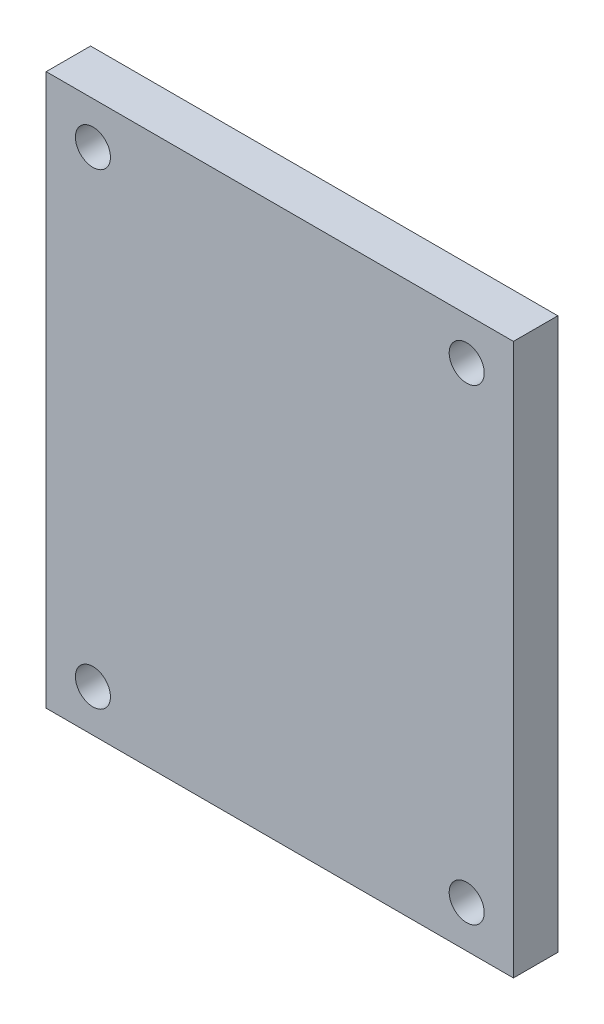
SolidWorks part; units mm, degrees
ref_plane "Front Plane" through (0, 0, 0) normal (0, 0, 1) x (1, 0, 0)
ref_plane "Top Plane" through (0, 0, 0) normal (0, 1, 0) x (1, 0, 0)
ref_plane "Right Plane" through (0, 0, 0) normal (1, 0, 0) x (0, 0, -1)
sketch "Sketch1" plane through (0, 0, 0) normal (0, 0, 1) x (1, 0, 0)
  line L0 (5.08, 55.372) -> (5.08, 4.572) construction
  line L1 (0, 0) -> (50.8, 0)
  line L2 (0, 0) -> (0, 59.944)
  line L3 (0, 59.944) -> (50.8, 59.944)
  line L4 (50.8, 0) -> (50.8, 59.944)
  line L5 (0, 29.972) -> (50.8, 29.972) construction
  line L6 (25.4, 59.944) -> (25.4, 29.972) construction
  circle A0 centre (5.08, 55.372) radius 1.905
  circle A1 centre (5.08, 4.572) radius 1.905
  circle A2 centre (45.72, 55.372) radius 1.905
  circle A3 centre (45.72, 4.572) radius 1.905
  dimension "D3" = 3.81
  dimension "D4" = 3.81
  dimension "D6" = 3.81
  dimension "D8" = 3.81
  dimension "D1" = 59.944
  dimension "D2" = 50.8
  dimension "D5" = 50.8
  dimension "D7" = 40.64
  dimension "D9" = 40.64
  dimension "D10" = 50.8
  dimension "D11" = 25.4
  dimension "D12" = 20.32
extrude "Boss-Extrude1" add sketch "Sketch1" along normal blind 4.826
equation "\"MDF\"= 0.19in"
equation "\"PVCID\" = 2.067in"
equation "\"PVCOD\" = 2.375in"
equation "\"GenDiameter\"= 60mm"
equation "\"GenCutDiameter\" = 1.8in"
equation "\"GenCutDistance\" = 1"
equation "\"TowerHeight\" = 6in"
equation "\"TowerFrontBase\" = 3in"
equation "\"FunnelHeight\" = 1in"
equation "\"FunnelAngle\" = 20"
equation "\"TowerSideBase\" = 3in"
equation "\"TowerPanelLength\" = 2in"
equation "\"TowerPanelLeeway\" = 0.5in"
equation "\"BaseLength\" = 9in"
equation "\"BaseWidth\" = 10in"
equation "\"WheelHoleLength\" = 3.25in"
equation "\"WheelHoleWidth\" = 26mm"
equation "\"WheelHoleFromBack\" = 1.5in"
equation "\"DropLength\" = 1in"
equation "\"DropWidth\" = 8.5in"
equation "\"BumperWidth\" = 2in"
equation "\"SmallHexDiameter\" = 0.185in"
equation "\"SmallHexHeight\" = 0.701in"
equation "\"ScrewSize\" = 0.106in"
equation "\"BigHexDiameter\" = 0.251in"
equation "\"BigHexHeight\" = 0.374in"
equation "\"PCBThickness\" = 0.066in"
equation "\"ConnectorHeight\" = 0.517in"
equation "\"BoardHeight\" = 0.583in"
equation "\"UnoStackHeight\" = 1.351in"
equation "\"UnoStackWidth\" = 3.053in"
equation "\"UnoStackLength\" = 3.152in"
equation "\"HBridgeWidth\" = 1.797in"
equation "\"HBridgeLength\" = 2.236in"
equation "\"DSWidth\" = 1.820in"
equation "\"DSLength\" = 1.833in"
equation "\"StepperWidth\" = 1.799in"
equation "\"StepperLength\" = 2.248in"
equation "\"ULNWidth\" = 1.304in"
equation "\"ULNLength\" = 1.545in"
equation "\"VSwitchHeight\" = 0.392in"
equation "\"VSwitchWidth\" = 0.637in"
equation "\"VSwitchLength\" = 1.097in"
equation "\"SkateWheelDiameter\" = 80mm"
equation "\"SkateWheelThickness\" = 24mm"
equation "\"BaseDistance\" = 3in"
equation "\"DummyVar\" = 2in"
equation "\"D1@Boss-Extrude1\"=\"MDF\""
